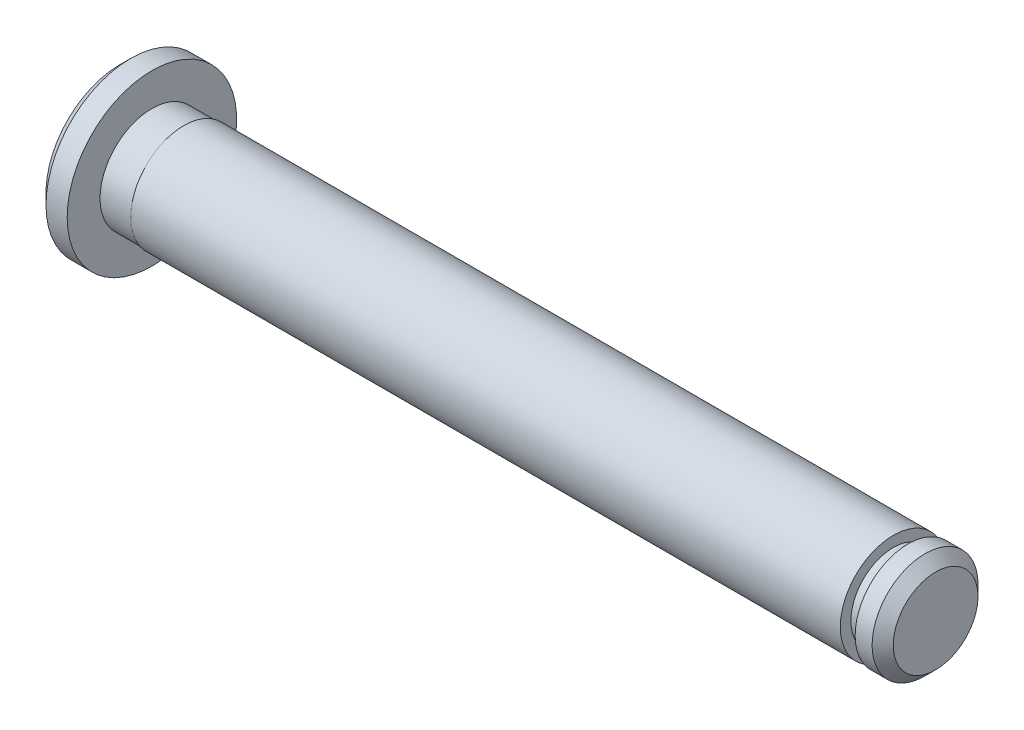
SolidWorks part; units mm, degrees
ref_plane "Front Plane" through (0, 0, 0) normal (0, 0, 1) x (1, 0, 0)
ref_plane "Top Plane" through (0, 0, 0) normal (0, 1, 0) x (1, 0, 0)
ref_plane "Right Plane" through (0, 0, 0) normal (1, 0, 0) x (0, 0, -1)
sketch "Sketch1" plane through (0, 0, 0) normal (0, 0, 1) x (1, 0, 0)
  line L0 (0, 0) -> (37, 0) construction
  line L1 (-1.5, 0) -> (-1.5, 4)
  line L2 (-1.5, 4) -> (0, 4)
  line L3 (0, 4) -> (0, 2.45)
  line L4 (0, 2.45) -> (1.5, 2.45)
  line L5 (37, 2.5) -> (37, 0)
  line L6 (-1.5, 0) -> (37, 0)
  line L7 (1.5, 2.45) -> (1.5, 2.5)
  line L8 (1.5, 2.5) -> (35, 2.5)
  line L9 (35, 2.5) -> (35, 2)
  line L10 (35, 2) -> (35.7, 2)
  line L11 (35.7, 2) -> (35.7, 2.5)
  line L12 (35.7, 2.5) -> (37, 2.5)
  dimension "L" = 35
  dimension "D_s" = 4
  dimension "H" = 8
  dimension "T" = 1.5
  dimension "N_s" = 1.5
  dimension "U_s" = 4.9
  dimension "M" = 0.7
  dimension "N" = 2
  dimension "D" = 5
revolve "Revolve1" add sketch "Sketch1" angle 360 about L0
chamfer "Chamfer1" distance 0.5 angle 45 2 edges at (-1.5, 0, 4) (37, 0, 2.5)
sketch "Sketch2" [suppressed] plane through (0, 0, 0) normal (0, 0, 1) x (1, 0, 0)
  line L0 (-1.5, 2.25) -> (-1.5, -2.25) construction
  line L3 (0, 0) -> (12, 0)
  line L4 (0, 0) -> (0, 1.5)
  line L5 (0, 1.5) -> (12, 1.5)
  line L6 (-1.5, 0) -> (12, 0) construction
  line L7 (12, -1) -> (12, 1) construction
  line L9 (12, 0) -> (12, 1.5)
  dimension "D" = 5
revolve "Cut-Revolve1" [suppressed] cut sketch "Sketch2" angle 360 about L6
sketch "Sketch3" [suppressed] plane through (0, 0, 0) normal (0, 0, 1) x (1, 0, 0)
  line L0 (0, 0) -> (11.5, 0) construction
  line L1 (0, -2.75) -> (0, 2.75) construction
  line L3 (0, 0) -> (0, 1.45)
  line L4 (0, 1.45) -> (1.5, 1.45)
  line L5 (11.5, 1.5) -> (11.5, 0)
  line L6 (0, 0) -> (11.5, 0)
  line L7 (1.5, 1.45) -> (1.5, 1.5)
  line L8 (1.5, 1.5) -> (10, 1.5)
  line L9 (10, 1.5) -> (10, 1)
  line L10 (10, 1) -> (10.5, 1)
  line L11 (10.5, 1) -> (10.5, 1.5)
  line L12 (10.5, 1.5) -> (11.5, 1.5)
  dimension "D" = 5
  dimension "L" = 35
  dimension "D_s" = 4
  dimension "N_s" = 1.5
  dimension "U_s" = 4.9
  dimension "M" = 0.7
  dimension "NC" = 1.5
revolve "Revolve2" [suppressed] add sketch "Sketch3" angle 360 about L0
chamfer "Chamfer2" [suppressed] distance 0.5 angle 45
sketch "Sketch4" [suppressed] plane through (0, 0, 0) normal (0, 0, 1) x (1, 0, 0)
  line L0 (-1.5, 2.25) -> (-1.5, -2.25) construction
  line L1 (-1.5, 2.75) -> (0, 2.75)
  line L2 (-1.5, 2.75) -> (-1.5, 0)
  line L3 (-1.5, 0) -> (0, 0)
  line L4 (0, 2.75) -> (0, 0)
  line L6 (0, -2.75) -> (0, 2.75) construction
  line L7 (0, 0) -> (-1.5, 0) construction
  dimension "H" = 8
revolve "Cut-Revolve2" [suppressed] cut sketch "Sketch4" angle 360 about L7
sketch "Sketch5" [suppressed] plane through (0, 0, 0) normal (0, 0, 1) x (1, 0, 0)
  line L1 (-2, 2.75) -> (0, 2.75)
  line L2 (-2, 2.75) -> (-2, 0)
  line L3 (-2, 0) -> (0, 0)
  line L4 (0, 2.75) -> (0, 0)
  line L7 (0, 0) -> (-2, 0) construction
  dimension "TC" = 2
  dimension "H" = 8
revolve "Revolve3" [suppressed] add sketch "Sketch5" angle 360 about L7
chamfer "Chamfer3" [suppressed] distance 0.5 angle 45
sketch "Sketch6" [suppressed] plane through (0, 0, 0) normal (1, 0, 0) x (0, 0, -1)
  line L0 (0, 0) -> (-2.75, 0) construction
  line L1 (-2.75, 2.75) -> (-1.75, 2.75)
  line L2 (-2.75, 2.75) -> (-2.75, -2.75)
  line L3 (-2.75, -2.75) -> (-1.75, -2.75)
  line L4 (-1.75, 2.75) -> (-1.75, -2.75)
  dimension "D2" = 4
  dimension "HC" = 3
  dimension "H" = 8
extrude "Cut-Extrude1" [suppressed] cut sketch "Sketch6" against normal through all
equation "\"D2@Sketch6\" = \"H@Sketch1\" / 2"
equation "\"HC@Sketch6\"=if ( \"D@Sketch1\" > 10 , \"H@Sketch1\" / 2 - 2 , \"H@Sketch1\" / 2 - 1 )"
